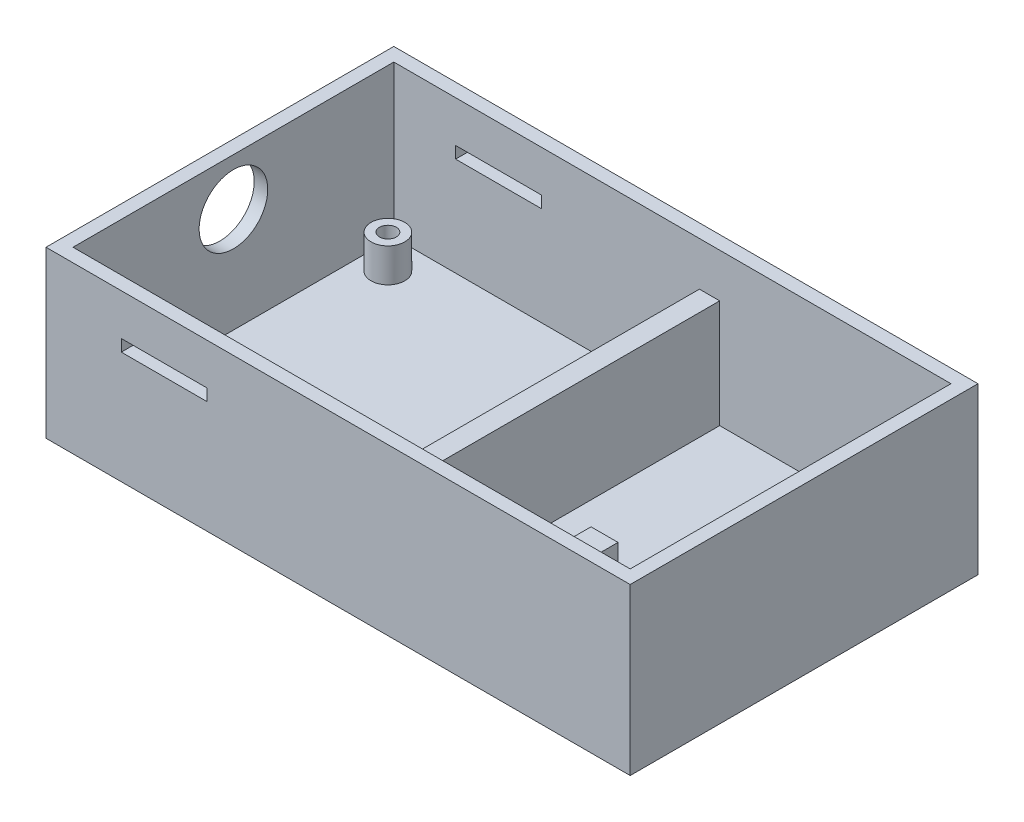
SolidWorks part; units mm, degrees
material "ABS"
ref_plane "Front Plane" through (0, 0, 0) normal (0, 0, 1) x (1, 0, 0)
ref_plane "Top Plane" through (0, 0, 0) normal (0, 1, 0) x (1, 0, 0)
ref_plane "Right Plane" through (0, 0, 0) normal (1, 0, 0) x (0, 0, -1)
sketch "Sketch1" plane through (0, 0, 0) normal (0, 1, 0) x (1, 0, 0)
  line L0 (86.5, 51.5) -> (-86.5, 51.5)
  line L1 (82.5, 47.5) -> (-82.5, 47.5)
  line L2 (82.5, 47.5) -> (82.5, -47.5)
  line L3 (82.5, -47.5) -> (-82.5, -47.5)
  line L4 (-82.5, 47.5) -> (-82.5, -47.5)
  line L5 (82.5, 47.5) -> (-82.5, -47.5) construction
  line L6 (82.5, -47.5) -> (-82.5, 47.5) construction
  line L7 (-86.5, 51.5) -> (-86.5, -51.5)
  line L8 (86.5, -51.5) -> (-86.5, -51.5)
  line L9 (86.5, 51.5) -> (86.5, -51.5)
  point P0 (0, 0)
  dimension "D1" = 165
  dimension "D2" = 95
  dimension "D3" = 4
extrude "Boss-Extrude1" add sketch "Sketch1" along normal blind 45 contours L1 L4 L3 L2 | L0 L7 L8 L9 region at (0, 0, 0)
extrude "Boss-Extrude2" add sketch "Sketch1<3>" against normal blind 4 contours L0 L7 L8 L9
sketch "Sketch1<3>" plane through (0, 0, 0) normal (0, 1, 0) x (1, 0, 0) same geometry as "Sketch1"
sketch "Sketch5" plane through (0, 0, 0) normal (0, 1, 0) x (1, 0, 0)
  line L0 (82.5, 47.5) -> (-82.5, 47.5) construction
  line L1 (8, 47.5) -> (14, 47.5)
  line L2 (8, 47.5) -> (8, -47.5)
  line L3 (8, -47.5) -> (14, -47.5)
  line L4 (14, 47.5) -> (14, -47.5)
  line L5 (82.5, -47.5) -> (-82.5, -47.5) construction
  line L6 (82.5, 47.5) -> (82.5, -47.5) construction
  dimension "D1" = 6
  dimension "D2" = 74.5
extrude "Boss-Extrude3" add sketch "Sketch5" along normal blind 32 contours L2 L3 L4 L1
sketch "Sketch6" plane through (0, 0, 0) normal (0, 1, 0) x (1, 0, 0)
  line L0 (-82.5, -47.5) -> (8, 47.5) construction
  line L1 (-82.5, 47.5) -> (8, -47.5) construction
  line L3 (0.25, -38) -> (-74.75, -38) construction
  line L4 (0.25, -38) -> (0.25, 38) construction
  line L5 (0.25, 38) -> (-74.75, 38) construction
  line L6 (-74.75, -38) -> (-74.75, 38) construction
  line L7 (0.25, -38) -> (-74.75, 38) construction
  line L8 (0.25, 38) -> (-74.75, -38) construction
  circle A0 centre (0.25, 38) radius 2.5
  circle A1 centre (-74.75, 38) radius 2.5
  circle A2 centre (0.25, -38) radius 2.5
  circle A3 centre (-74.75, -38) radius 5
  circle A4 centre (-74.75, -38) radius 2.5
  circle A5 centre (0.25, -38) radius 5
  circle A6 centre (-74.75, 38) radius 5
  circle A7 centre (0.25, 38) radius 5
  point P8 (-37.25, 0)
  point P9 (-37.25, 0)
  dimension "D3" = 10
  dimension "D4" = 5
  dimension "D1" = 76
  dimension "D2" = 75
extrude "StandoffInserts" add sketch "Sketch6" along normal blind 10 contours A7 | A5 | A2 | A3 | A4 | A6 | A1 | A0
sketch "Sketch7" plane through (0, 0, -51.5) normal (0, 0, -1) x (-1, 0, 0)
  line L0 (-86.5, -4) -> (86.5, -4) construction
  line L1 (86.5, 45) -> (86.5, -4) construction
  line L3 (38.8, 32.75) -> (64.2, 32.75)
  line L4 (38.8, 32.75) -> (38.8, 29.25)
  line L5 (38.8, 29.25) -> (64.2, 29.25)
  line L6 (64.2, 32.75) -> (64.2, 29.25)
  line L7 (38.8, 32.75) -> (64.2, 29.25) construction
  line L8 (38.8, 29.25) -> (64.2, 32.75) construction
  point P0 (51.5, 31)
  point P12 (0, 0)
  point P13 (0, 0)
  dimension "D1" = 25.4
  dimension "D2" = 3.5
  dimension "D3" = 35
  dimension "D4" = 35
extrude "Cut-Extrude1" cut sketch "Sketch7" against normal through all
sketch "Sketch8" plane through (0, 0, 0) normal (0, 1, 0) x (1, 0, 0)
  line L0 (82.5, -47.5) -> (-82.5, -47.5) construction
  line L1 (45.9012, -47.5) -> (53.9012, -47.5)
  line L2 (45.9012, -47.5) -> (45.9012, -22.5)
  line L3 (45.9012, -22.5) -> (53.9012, -22.5) construction
  line L4 (53.9012, -47.5) -> (53.9012, -22.5)
  line L5 (53.9012, -22.5) -> (45.9012, -22.5)
  dimension "D1" = 25
  dimension "D2" = 8
extrude "Boss-Extrude5" add sketch "Sketch8" along normal blind 25 contours L5 L2 L1 L4
sketch "Sketch9" plane through (-86.5, 0, 0) normal (-1, 0, 0) x (0, 0, 1)
  line L2 (-51.5, -4) -> (51.5, -4) construction
  circle A0 centre (0, 31) radius 10.16
  point P0 (0, 23.3161)
  point P4 (0, 0)
  point P8 (0, 0)
  dimension "D1" = 20.32
  dimension "D2" = 35
extrude "Cut-Extrude2" cut sketch "Sketch9" against normal blind 10 contours A0
